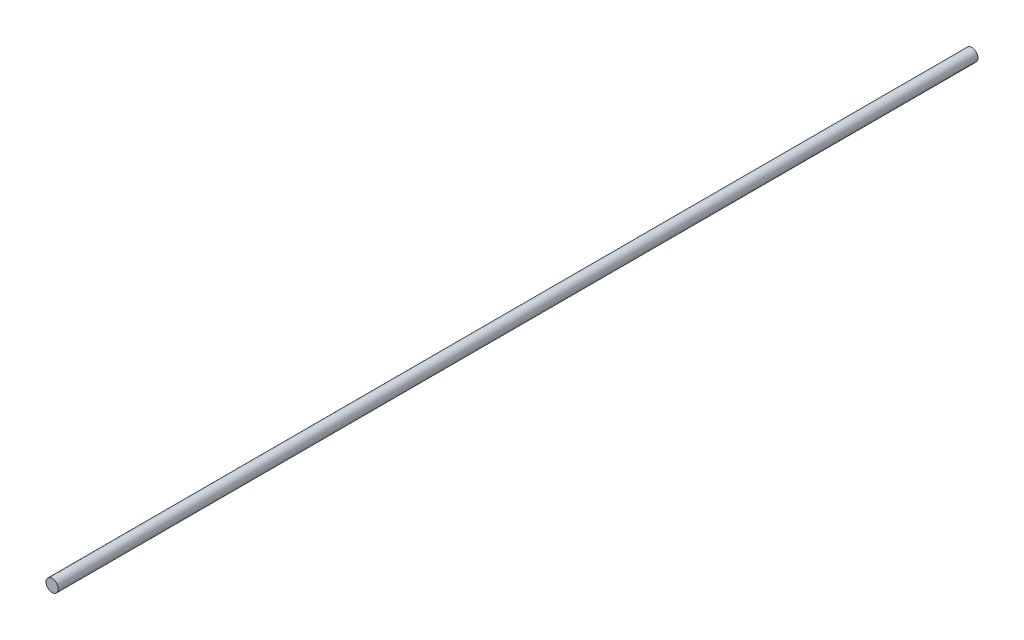
SolidWorks part; units mm, degrees
material "Ст 3 ГОСТ 380-88"
ref_plane "Спереди" through (0, 0, 0) normal (0, 0, 1) x (1, 0, 0)
ref_plane "Сверху" through (0, 0, 0) normal (0, 1, 0) x (1, 0, 0)
ref_plane "Справа" through (0, 0, 0) normal (1, 0, 0) x (0, 0, -1)
sketch "Эскиз1" plane through (0, 0, 0) normal (0, 0, 1) x (1, 0, 0)
  circle A0 centre (0, 0) radius 10
  circle A1 centre (0, 0) radius 50 construction
  point P5 (0, 0)
  dimension "D1" = 20
  dimension "D2" = 100
extrude "Бобышка-Вытянуть1" add sketch "Эскиз1" along normal blind 1480 and the other way blind 20
ref_axis "Axis1" through (0, 0, -75) along (0, 0, 1)
ref_plane "Plane1" through (0, 0, 730) normal (0, 0, 1) x (1, 0, 0)
